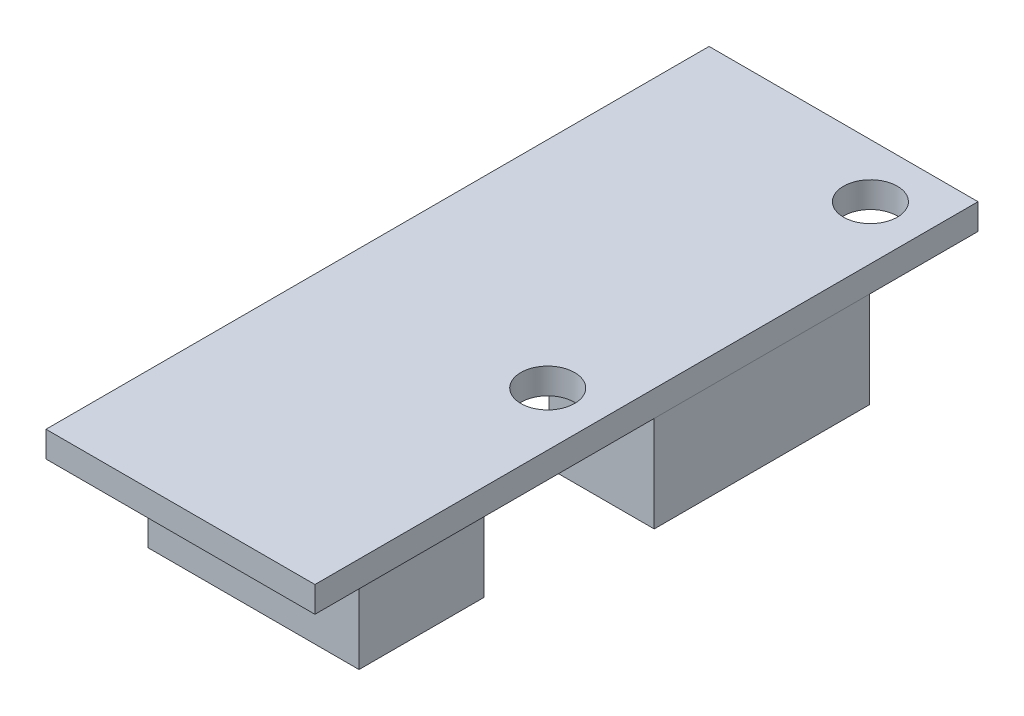
SolidWorks part; units mm, degrees
ref_plane "Front Plane" through (0, 0, 0) normal (0, 0, 1) x (1, 0, 0)
ref_plane "Top Plane" through (0, 0, 0) normal (0, 1, 0) x (1, 0, 0)
ref_plane "Right Plane" through (0, 0, 0) normal (1, 0, 0) x (0, 0, -1)
sketch "Sketch1" plane through (0, 0, 0) normal (0, 1, 0) x (1, 0, 0)
  line L0 (-7.9375, 19.05) -> (7.9375, 19.05) construction
  line L1 (0, 22.225) -> (0, -16.9164) construction
  line L2 (-7.9375, -16.9164) -> (-7.9375, 22.225)
  line L3 (-7.9375, 22.225) -> (7.9375, 22.225)
  line L4 (7.9375, -16.9164) -> (7.9375, 22.225)
  line L5 (4.7625, 19.05) -> (4.7625, 0)
  line L7 (4.7625, -16.9164) -> (4.7625, 22.225) construction
  line L8 (-7.9375, 22.225) -> (-7.9375, -16.9164)
  line L9 (-7.9375, -16.9164) -> (7.9375, -16.9164)
  line L10 (4.7625, -22.225) -> (4.7625, 22.225) construction
  line L11 (7.9375, -22.225) -> (7.9375, 22.225) construction
  line L12 (1.651, 3.175) -> (7.874, 3.175)
  line L13 (1.651, 3.175) -> (1.651, 15.875)
  line L14 (1.651, 15.875) -> (7.874, 15.875)
  line L15 (7.874, 3.175) -> (7.874, 15.875)
  line L16 (1.651, 3.175) -> (7.874, 15.875) construction
  line L17 (1.651, 15.875) -> (7.874, 3.175) construction
  circle A0 centre (4.7625, 19.05) radius 1.5875
  circle A1 centre (4.7625, 0) radius 1.5875
  point P0 (0, 0)
  point P18 (4.7625, 9.525)
  dimension "D5" = 6.223
  dimension "D2" = 12.7
  dimension "D1" = 15.875
  dimension "D3" = 3.175
  dimension "D4" = 3.175
extrude "Boss-Extrude1" add sketch "Sketch1" along normal blind 1.524 contours L2 L9 L4 L3 A1 L12 L13 L14 A0 L15 region at (-0.8581, 0, -1.4163)
extrude "Boss-Extrude2" add sketch "Sketch1<4>" along normal blind 1.524 contours L14 L13 L12 L5 | L12 L15 L14 L5 region at (6.3183, 0, -9.525) region at (3.2068, 0, -9.525)
sketch "Sketch1<4>" plane through (0, 0, 0) normal (0, 1, 0) x (1, 0, 0) same geometry as "Sketch1"
extrude "Boss-Extrude3" add sketch "Sketch1<5>" against normal blind 5.715 contours L12 L15 L14 L5 | L14 L13 L12 L5 region at (6.3183, 0, -9.525) region at (3.2068, 0, -9.525)
sketch "Sketch1<5>" plane through (0, 0, 0) normal (0, 1, 0) x (1, 0, 0) same geometry as "Sketch1"
sketch "Sketch2" plane through (0, 0, 0) normal (0, -1, 0) x (1, 0, 0)
  line L0 (0, 16.9164) -> (0, 5.2324)
  line L1 (-7.9375, 16.9164) -> (7.9375, 16.9164) construction
  line L2 (0, 5.2324) -> (0, 12.5984)
  line L4 (-6.223, 12.5984) -> (6.223, 12.5984)
  line L5 (-6.223, 12.5984) -> (-6.223, 5.2324)
  line L6 (-6.223, 5.2324) -> (6.223, 5.2324)
  line L7 (6.223, 12.5984) -> (6.223, 5.2324)
  line L8 (-6.223, 12.5984) -> (6.223, 5.2324) construction
  line L9 (-6.223, 5.2324) -> (6.223, 12.5984) construction
  point P5 (0, 8.9154)
  dimension "D1" = 7.366
  dimension "D2" = 12.446
extrude "Boss-Extrude4" add sketch "Sketch2" along normal blind 5.842 contours L7 L4 L0 L6 | L5 L6 L0 L4 region at (3.1115, 0, 8.9154) region at (-3.1115, 0, 8.9154)
sketch "Sketch3" plane through (0, 1.524, 0) normal (0, 1, 0) x (1, 0, 0)
  line L4 (-7.9375, 22.225) -> (-7.9375, -16.9164)
  line L5 (-7.9375, -16.9164) -> (7.9375, -16.9164)
  line L6 (7.9375, -16.9164) -> (7.9375, 22.225)
  line L7 (7.9375, 22.225) -> (-7.9375, 22.225)
  line L8 (-7.9375, 22.225) -> (-7.9375, -16.9164)
  line L9 (-7.9375, -16.9164) -> (7.9375, -16.9164)
  line L10 (7.9375, -16.9164) -> (7.9375, 22.225)
  line L11 (7.9375, 22.225) -> (-7.9375, 22.225)
  circle A0 centre (4.7625, 19.05) radius 1.5875 construction
  circle A1 centre (4.7625, 0) radius 1.5875 construction
  circle A2 centre (4.7625, 19.05) radius 1.5875
  circle A3 centre (4.7625, 0) radius 1.5875
  dimension "D1" = 0
